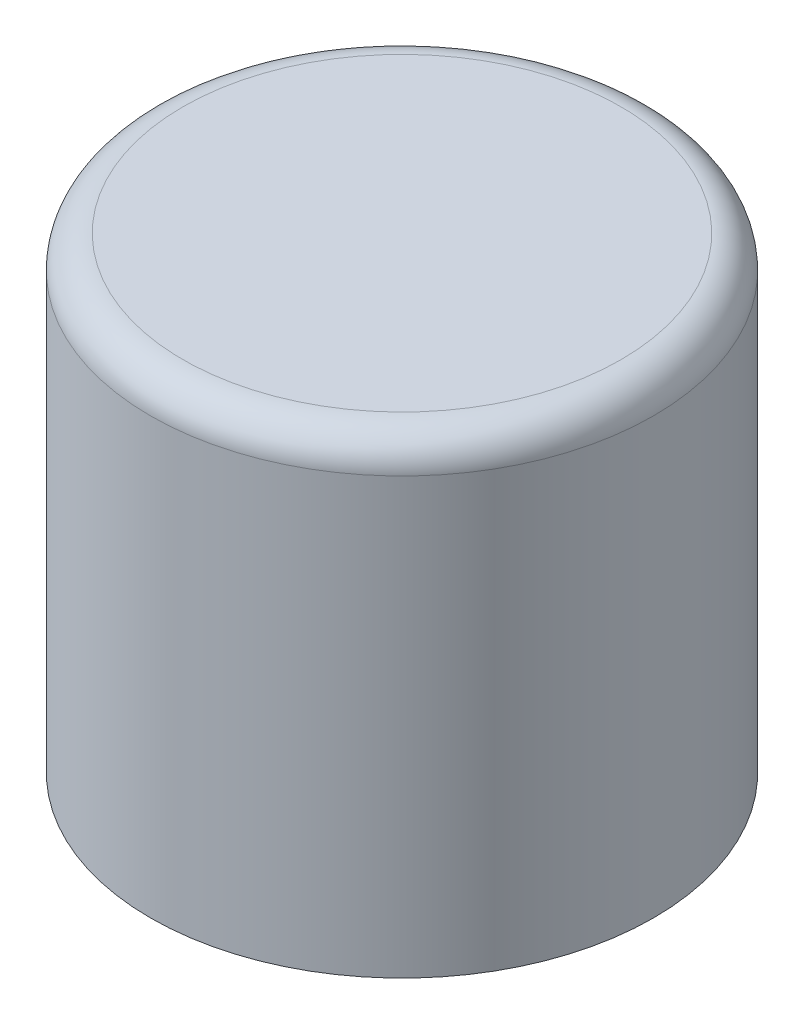
SolidWorks part; units mm, degrees
ref_plane "Plan de face" through (0, 0, 0) normal (0, 0, 1) x (1, 0, 0)
ref_plane "Plan de dessus" through (0, 0, 0) normal (0, 1, 0) x (1, 0, 0)
ref_plane "Plan de droite" through (0, 0, 0) normal (1, 0, 0) x (0, 0, -1)
sketch "Esquisse1" plane through (0, 0, 0) normal (0, 0, 1) x (1, 0, 0)
  line L0 (0, 0) -> (0, 28.8) construction
  line L2 (-15.5, 0) -> (-15.5, 28.8)
  line L3 (-15.5, 28.8) -> (0, 28.8)
  line L4 (0, 28.8) -> (0, 25.8)
  line L5 (0, 25.8) -> (-14.5, 25.8) construction
  line L6 (-14.5, 25.8) -> (-14.5, 2.6) construction
  line L7 (-14.5, 2.6) -> (-14, 2.6)
  line L8 (-14, 2.6) -> (-14, 1.6)
  line L9 (-14, 1.6) -> (-14.5, 1.6)
  line L10 (-14.5, 1.6) -> (-14.5, 1)
  line L11 (-14.5, 1) -> (-14, 1)
  line L12 (-14, 1) -> (-14, 0)
  line L17 (-14, 0) -> (-15.5, 0)
  line L18 (-14.5, 2.6) -> (-14.5, 3.2)
  line L19 (-14.5, 3.2) -> (-12, 3.2)
  line L20 (-12, 3.2) -> (-12, 25.8)
  line L21 (-12, 25.8) -> (0, 25.8)
  point P16 (-13.9, 0.5827)
  point P17 (-12, 3.7628)
  dimension "D1" = 1
  dimension "D2" = 0.6
  dimension "D3" = 15.5
  dimension "D4" = 0.6
  dimension "D5" = 0.5
  dimension "D6" = 12
  dimension "D7" = 25.8
  dimension "D8" = 1.5
  dimension "D9" = 3
revolve "Révolution1" add sketch "Esquisse1" angle 360 about L0
fillet "Congé1" radius 2 1 edges at (15.5, 28.8, 0)
